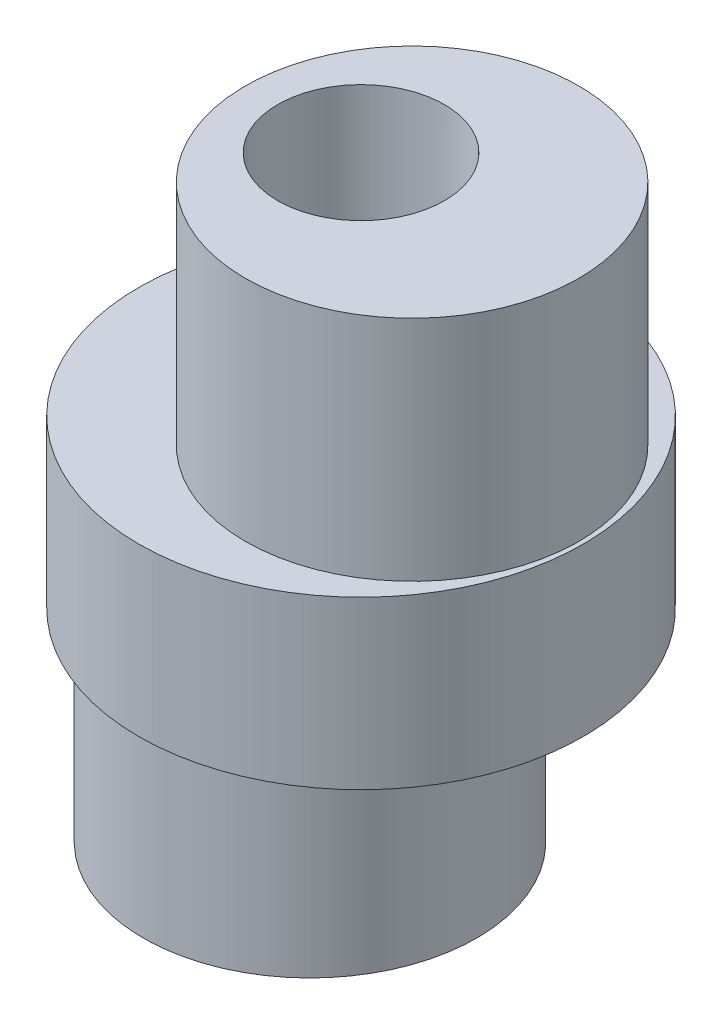
SolidWorks part; units mm, degrees
ref_plane "Front Plane" through (0, 0, 0) normal (0, 0, 1) x (1, 0, 0)
ref_plane "Top Plane" through (0, 0, 0) normal (0, 1, 0) x (1, 0, 0)
ref_plane "Right Plane" through (0, 0, 0) normal (1, 0, 0) x (0, 0, -1)
sketch "Sketch1" plane through (0, 0, 0) normal (0, 1, 0) x (1, 0, 0)
  circle A0 centre (0, 0) radius 8
  dimension "D1" = 16
extrude "Boss-Extrude1" add sketch "Sketch1" along normal blind 6
sketch "Sketch2" plane through (0, 6, 0) normal (0, 1, 0) x (1, 0, 0)
  circle A0 centre (1.8375, 0) radius 6
  dimension "D1" = 12
  dimension "D2" = 1.8375
extrude "Boss-Extrude2" add sketch "Sketch2" along normal blind 8.2
sketch "Sketch3" plane through (0, 0, 0) normal (0, -1, 0) x (1, 0, 0)
  circle A0 centre (-1.8375, 0) radius 6
  dimension "D2" = 12
  dimension "D1" = 1.8375
extrude "Boss-Extrude3" add sketch "Sketch3" along normal blind 8.2
sketch "Sketch4" plane through (0, 6, 0) normal (0, 1, 0) x (1, 0, 0)
  circle A0 centre (0, 0) radius 3
  dimension "D1" = 6
extrude "Cut-Extrude1" cut sketch "Sketch4" against normal mid plane 30
